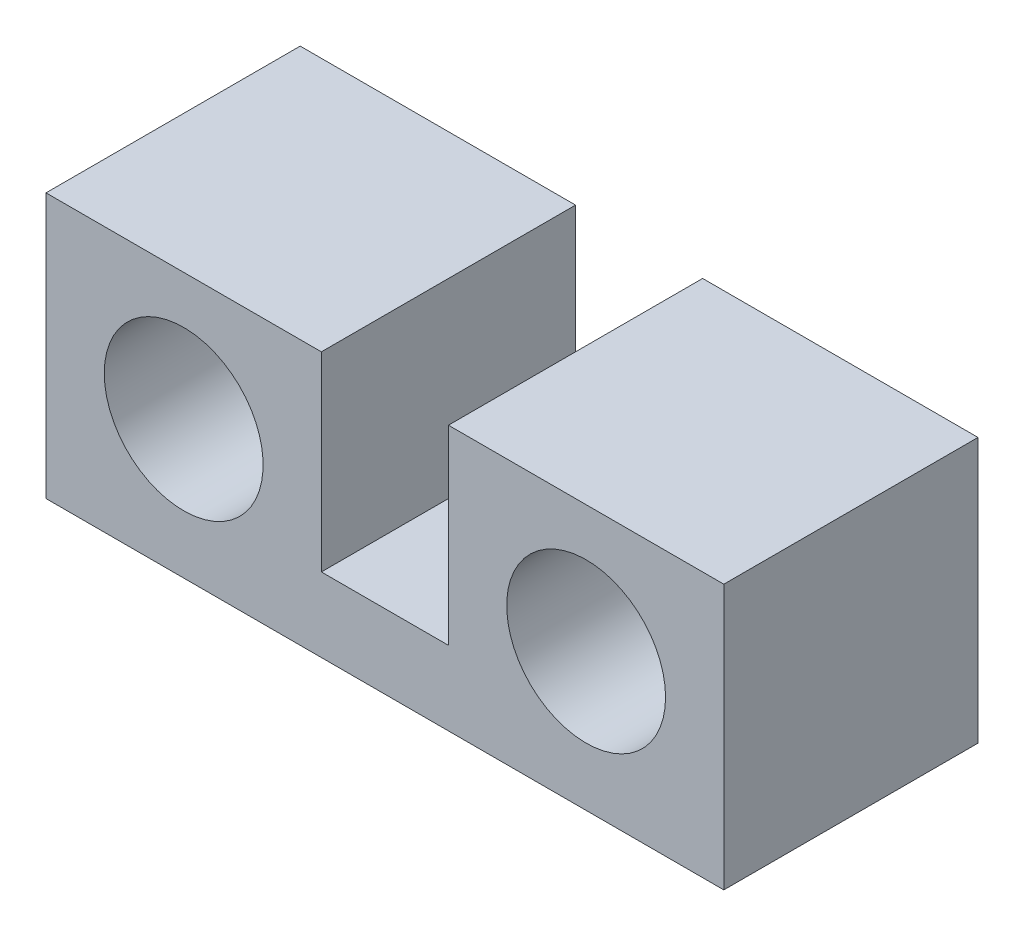
SolidWorks part; units mm, degrees
ref_plane "Front Plane" through (0, 0, 0) normal (0, 0, 1) x (1, 0, 0)
ref_plane "Top Plane" through (0, 0, 0) normal (0, 1, 0) x (1, 0, 0)
ref_plane "Right Plane" through (0, 0, 0) normal (1, 0, 0) x (0, 0, -1)
sketch "Sketch8" plane through (0, 0, 0) normal (0, 0, 1) x (1, 0, 0)
  line L0 (0, 0) -> (0, 26.9227) construction
  line L1 (0, 0) -> (32, 0)
  line L2 (32, 0) -> (32, 25)
  line L3 (32, 25) -> (6, 25)
  line L4 (6, 25) -> (6, 7)
  line L5 (6, 7) -> (0, 7)
  line L6 (0, 7) -> (0, 0)
  line L7 (19, 25) -> (19, 0) construction
  circle A0 centre (19, 13) radius 7.5
  dimension "D5" = 15
  dimension "D6" = 13
  dimension "D1" = 7
  dimension "D2" = 25
  dimension "D3" = 26
  dimension "D4" = 6
extrude "Boss-Extrude1" add sketch "Sketch8" along normal blind 12 and the other way blind 12
mirror "Mirror1" about plane through (0, 0, 0) normal (1, 0, 0) of "Boss-Extrude1"
